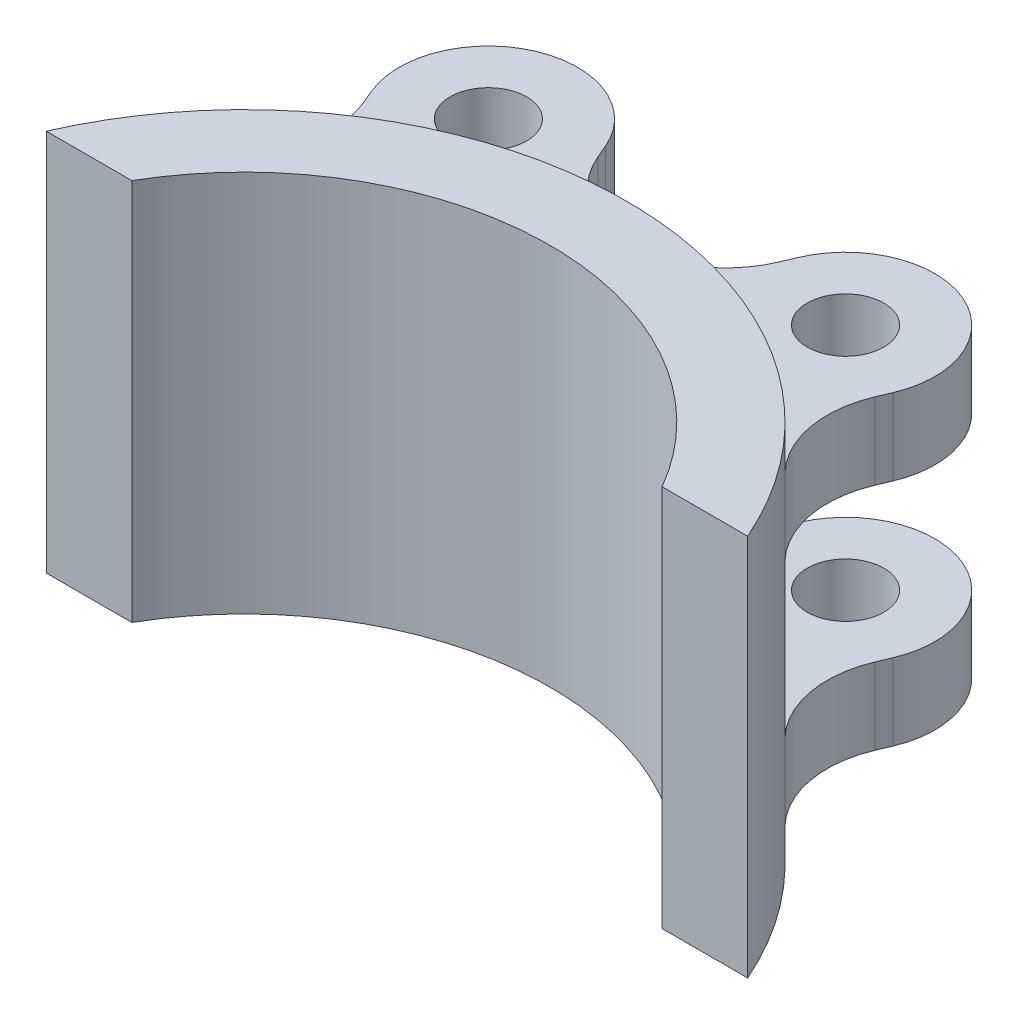
SolidWorks part; units mm, degrees
ref_plane "Plan de face" through (0, 0, 0) normal (0, 0, 1) x (1, 0, 0)
ref_plane "Plan de dessus" through (0, 0, 0) normal (0, 1, 0) x (1, 0, 0)
ref_plane "Plan de droite" through (0, 0, 0) normal (1, 0, 0) x (0, 0, -1)
sketch "Esquisse1" plane through (0, 0, 0) normal (0, 1, 0) x (1, 0, 0)
  line L0 (-12.9904, 7.5) -> (-10.3923, 6) construction
  line L1 (0, 40.2644) -> (0, -32.3317) construction
  line L2 (0, 15) -> (0, 12)
  line L4 (-10.3923, 6) -> (-13.7477, 6)
  arc A0 (0, 12) -> (-10.3923, 6) centre (0, 0) ccw
  arc A1 (0, 15) -> (-13.7477, 6) centre (0, 0) ccw
  dimension "D1" = 24
  dimension "D2" = 30
  dimension "D3" = 60
  dimension "D4" = 6
extrude "Boss.-Extru.1" add sketch "Esquisse1" along normal blind 7.5 and the other way blind 7.5
sketch "Esquisse2" plane through (0, 0, 0) normal (0, 1, 0) x (1, 0, 0)
  line L0 (0, 0) -> (-7, 16.5831) construction
  line L1 (-10.2245, 15.222) -> (-8.8968, 12.0767)
  line L2 (-3.7755, 17.9442) -> (-2.4478, 14.7989)
  circle A0 centre (-7, 16.5831) radius 1.5
  arc A1 (-3.7755, 17.9442) -> (-10.2245, 15.222) centre (-7, 16.5831) ccw
  arc A2 (-2.4478, 14.7989) -> (-8.8968, 12.0767) centre (0, 0) ccw
  arc A3 (0, 15) -> (-13.7477, 6) centre (0, 0) ccw construction
  dimension "D1" = 3
  dimension "D2" = 7
  dimension "D3" = 18
  dimension "D4" = 7
extrude "Boss.-Extru.2" add sketch "Esquisse2" along normal blind 6 and the other way blind 6
fillet "Congé2" radius 4 2 edges at (-2.4478, 0, -14.7989) (-8.8968, 0, -12.0767)
mirror "Symétrie1" about plane through (0, -7.5, -15) normal (1, 0, 0) of "Boss.-Extru.2", "Congé2", "Boss.-Extru.1"
sketch "Esquisse3" plane through (0, 0, 0) normal (0, 1, 0) x (1, 0, 0)
  circle A0 centre (0, 0) radius 15
  circle A1 centre (0, 0) radius 23.0033
extrude "Enlèv. mat.-Extru.1" cut sketch "Esquisse3" against normal blind 3 and the other way blind 3
